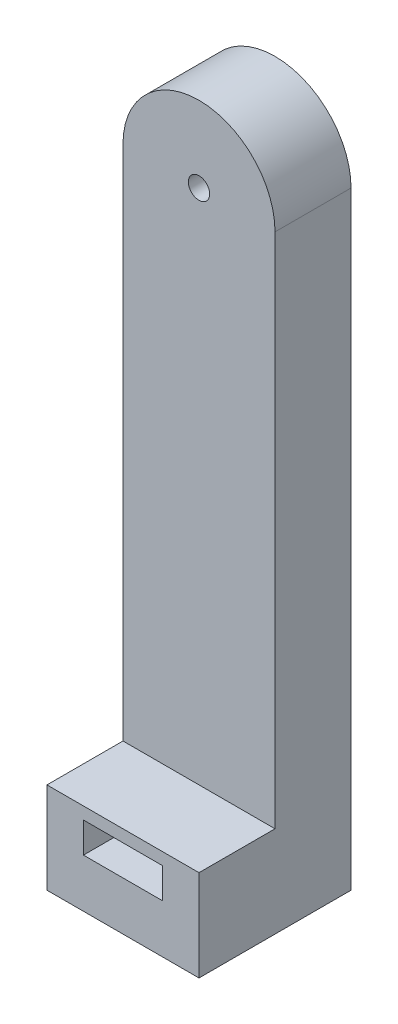
SolidWorks part; units mm, degrees
ref_plane "Front Plane" through (0, 0, 0) normal (0, 0, 1) x (1, 0, 0)
ref_plane "Top Plane" through (0, 0, 0) normal (0, 1, 0) x (1, 0, 0)
ref_plane "Right Plane" through (0, 0, 0) normal (1, 0, 0) x (0, 0, -1)
sketch "Sketch1" plane through (0, 0, 0) normal (0, 0, 1) x (1, 0, 0)
  line L0 (0, 0) -> (-12.5, 0)
  line L1 (-12.5, 0) -> (-12.5, 100)
  line L3 (12.5, 100) -> (12.5, 0)
  line L4 (12.5, 0) -> (0, 0)
  line L5 (0, 0) -> (0, 100) construction
  line L6 (-6.5, 13) -> (6.5, 13)
  line L7 (-6.5, 13) -> (-6.5, 8)
  line L8 (-6.5, 8) -> (6.5, 8)
  line L9 (6.5, 13) -> (6.5, 8)
  arc A0 (-12.5, 100) -> (12.5, 100) centre (0, 100) cw
  circle A1 centre (0, 100) radius 1.75
  dimension "D5" = 3.5
  dimension "D1" = 25
  dimension "D2" = 100
  dimension "D3" = 8
  dimension "D4" = 6
  dimension "D6" = 5
extrude "Boss-Extrude1" add sketch "Sketch1" along normal blind 25
sketch "Sketch4" plane through (0, 0, 0) normal (0, -1, 0) x (-1, 0, 0)
  line L3 (-12.5, -12.5) -> (12.5, -12.5) construction
  line L4 (-12.5, -25) -> (-12.5, 0) construction
  line L5 (12.5, -25) -> (12.5, 0) construction
  point P0 (0, -12.5)
hole_wizard "Ø10.0mm Dowel Hole1" positions "Sketch4" profile "Sketch3" hole size "Ø10.0" standard "ANSI Metric" end condition up to next
sketch "Sketch3" plane through (0, 0, 12.5) normal (1, 0, 0) x (0, 0, -1)
  line L0 (0, 0) -> (0, 8)
  line L1 (0, 8) -> (5, 8)
  line L2 (5, 8) -> (5, 0.025)
  line L3 (5, 0.025) -> (5.025, 0)
  line L5 (5.025, 0) -> (0, 0)
  line L6 (-5, 0.025) -> (-5.025, 0) construction
  line L11 (0, -6.35) -> (0, 107.95) construction
  dimension "Thru Hole Dia." = 10
  dimension "Thru Hole Depth" = 8
  dimension "Near C'Sink Dia." = 10.05
  dimension "Near C'Sink Angle" = 90
sketch "Sketch5" plane through (12.5, 0, 0) normal (1, 0, 0) x (0, 0, -1)
  line L0 (-25, 0) -> (-25, 100) construction
  line L1 (-25, 15) -> (-12.5, 15)
  line L2 (-25, 15) -> (-25, 112.5)
  line L3 (-25, 112.5) -> (-12.5, 112.5)
  line L4 (-12.5, 15) -> (-12.5, 112.5)
  line L5 (0, 112.5) -> (-25, 112.5) construction
  line L6 (-25, 0) -> (0, 0) construction
  line L7 (0, 0) -> (0, 100) construction
  dimension "D1" = 15
  dimension "D2" = 12.5
extrude "Cut-Extrude1" cut sketch "Sketch5" against normal through all
